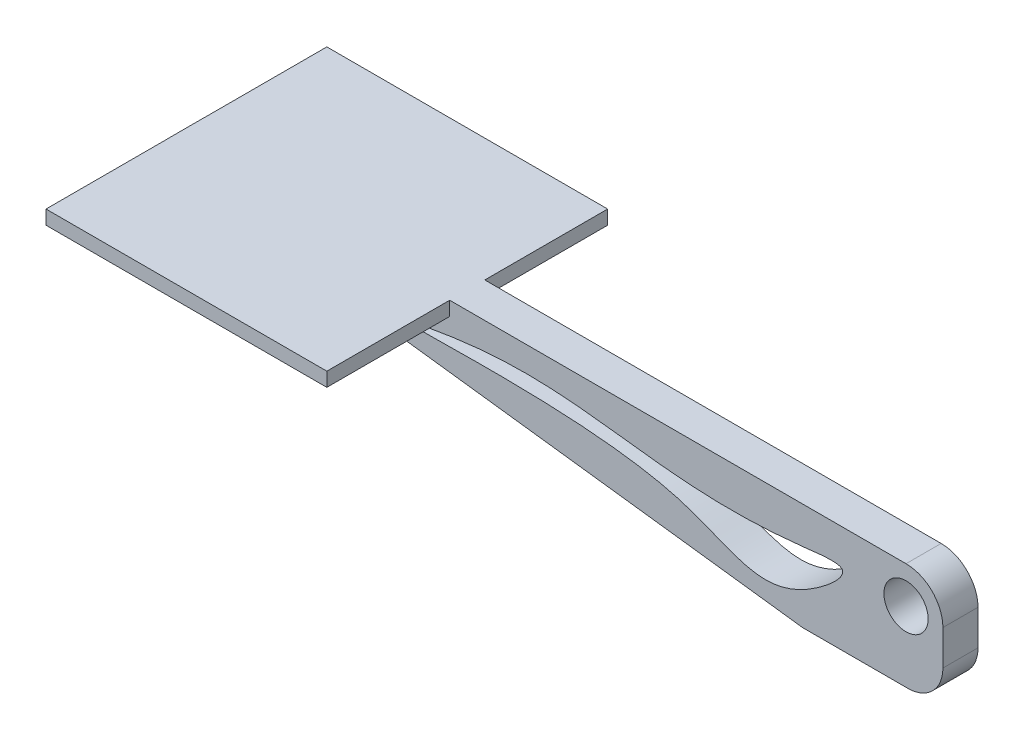
SolidWorks part; units mm, degrees
material "PET"
ref_plane "Front Plane" through (0, 0, 0) normal (0, 0, 1) x (1, 0, 0)
ref_plane "Top Plane" through (0, 0, 0) normal (0, 1, 0) x (1, 0, 0)
ref_plane "Right Plane" through (0, 0, 0) normal (1, 0, 0) x (0, 0, -1)
sketch "Sketch1" plane through (0, 0, 0) normal (0, 0, 1) x (1, 0, 0)
  line L1 (-171.2615, -2.2056) -> (-202.5166, -2.2056)
  line L2 (-210.0166, 5.2944) -> (-210.0166, 10.5)
  line L3 (0, 10.5) -> (-170, 10.5)
  line L4 (-170, 10.5) -> (-170, -2.2056)
  line L5 (-210.0166, 10.5) -> (-170, 10.5)
  line L6 (10.5, 0) -> (10.5, -10)
  line L7 (0.5, -20) -> (-29.5, -20)
  line L8 (-29.5, -20) -> (-168.7485, -2.3641)
  circle A0 centre (0, 0) radius 6.3
  circle A1 centre (0, 0) radius 10.5
  arc A2 (-202.5166, -2.2056) -> (-210.0166, 5.2944) centre (-202.5166, 5.2944) cw
  arc A3 (-171.2615, -2.2056) -> (-168.7485, -2.3641) centre (-171.2615, -22.2056) cw
  arc A4 (0.5, -20) -> (10.5, -10) centre (0.5, -10) ccw
  spline S0 degree 3 poles (-11.8774, 2.3896) (-69.1666, -5.9397) (-91.2496, 8.2956) (-167.3142, -4.5164) (-66.6605, 5.706) (-39.3547, -20.8236) (-11.8774, 2.3896) (-69.1666, -5.9397) (-91.2496, 8.2956) knots -0.251012 -0.108125 -0.045537 0 0.381705 0.44528 0.748988 0.891875 0.954463 1 1.381705 1.44528 1.748988 only from (-29.5, 0) to (-29.5, 0)
  point P23 (10.5, -20)
  dimension "D1" = 12.6
  dimension "D2" = 21
  dimension "D8" = 7.5
  dimension "D9" = 20
  dimension "D10" = 10
  dimension "D3" = 170
  dimension "D4" = 20
  dimension "D5" = 40.0166
  dimension "D6" = 40
extrude "Boss-Extrude2" add sketch "Sketch1" along normal blind 5 and the other way blind 5 contours A1 A0 | A1 L3 L4 | L5 L2 L1 L4 region at (-186.889, 0.0206, 0) region at (7.2146, 7.2146, 0)
sketch "Sketch2" plane through (0, 10.5, 0) normal (0, 1, 0) x (1, 0, 0)
  line L0 (0, 0) -> (-170, 0)
  line L1 (-171.2615, 0) -> (-202.5166, 0) construction
  line L3 (-210, -40) -> (-130, -40)
  line L4 (-210, -40) -> (-210, 40)
  line L5 (-210, 40) -> (-130, 40)
  line L6 (-130, -40) -> (-130, 40)
  line L7 (-210, -40) -> (-130, 40) construction
  line L8 (-210, 40) -> (-130, -40) construction
  line M2 (-210.0166, 5) -> (-210.0166, -5)
  line M3 (-210.0166, -5) -> (0, -5)
  line M5 (0, 5) -> (-210.0166, 5)
  dimension "D1" = 170
  dimension "D2" = 80
  dimension "D3" = 80
extrude "Boss-Extrude5" add sketch "Sketch2" against normal blind 4 contours L3 L6 L5 L4 M3 M2 M5 | L6 M3 M5 M2 | L4 L3 L6 L5 region at (-209.1938, 10.5, 0) region at (-170, 10.5, -22.5)
